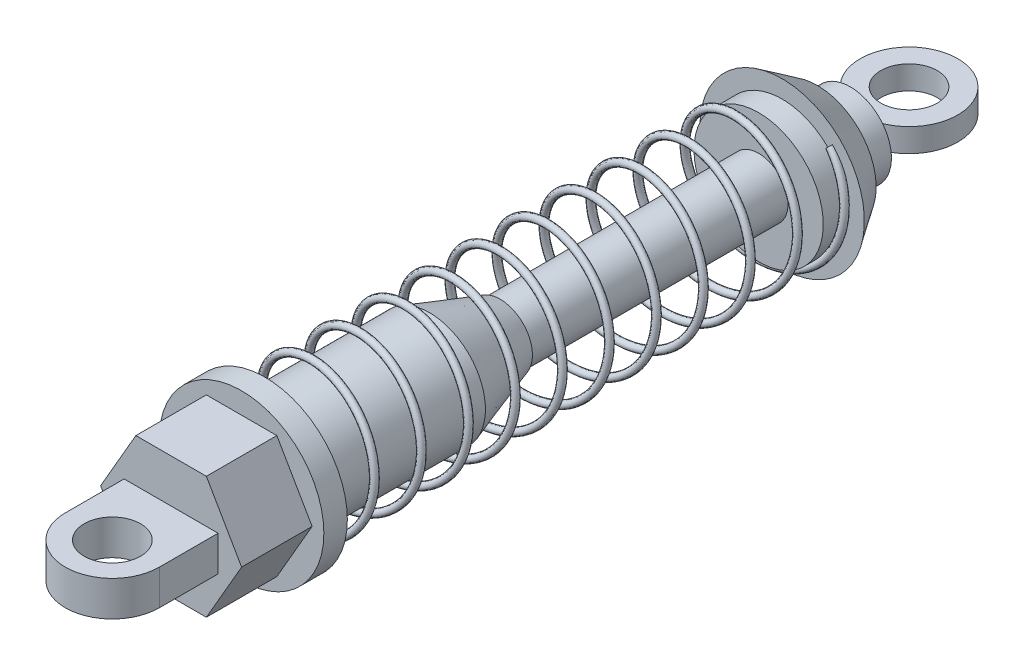
SolidWorks part; units mm, degrees
ref_plane "Alzado" through (0, 0, 0) normal (0, 0, 1) x (1, 0, 0)
ref_plane "Planta" through (0, 0, 0) normal (0, 1, 0) x (1, 0, 0)
ref_plane "Vista lateral" through (0, 0, 0) normal (1, 0, 0) x (0, 0, -1)
sketch "Croquis1" plane through (0, 0, 0) normal (0, 0, 1) x (1, 0, 0)
  circle A0 centre (0, 0) radius 7
  dimension "D1" = 14
extrude "Saliente-Extruir1" add sketch "Croquis1" along normal blind 2
sketch "Croquis2" plane through (0, 0, 2) normal (0, 0, 1) x (1, 0, 0)
  line L0 (0, 0) -> (-6, 0) construction
  line L1 (-3, 5.1962) -> (-6, 0)
  line L2 (-6, 0) -> (-3, -5.1962)
  line L3 (-3, -5.1962) -> (3, -5.1962)
  line L4 (3, -5.1962) -> (6, 0)
  line L5 (6, 0) -> (3, 5.1962)
  line L6 (3, 5.1962) -> (-3, 5.1962)
  dimension "D1" = 6
extrude "Saliente-Extruir2" add sketch "Croquis2" along normal blind 6
sketch "Croquis4" plane through (0, 0, 0) normal (0, 1, 0) x (1, 0, 0)
  line L0 (-6, -8) -> (-4, -8) construction
  line L1 (-3, -8) -> (-6, -8) construction
  line L3 (-4, -8) -> (4, -8)
  line L4 (-4, -8) -> (-4, -13)
  line L6 (4, -8) -> (4, -13)
  arc A0 (-4, -13) -> (4, -13) centre (0, -13) ccw
  dimension "D1" = 2
  dimension "D2" = 8
  dimension "D3" = 5
extrude "Saliente-Extruir3" add sketch "Croquis4" along normal mid plane 3
sketch "Croquis6" plane through (0, 1.5, 0) normal (0, 1, 0) x (1, 0, 0)
  circle A0 centre (0, -13) radius 2.4
  dimension "D1" = 4.8
extrude "Cortar-Extruir1" cut sketch "Croquis6" against normal blind 3
sketch "Croquis7" plane through (0, 0, 0) normal (0, 0, -1) x (-1, 0, 0)
  circle A0 centre (0, 0) radius 4.75
  dimension "D1" = 9.5
extrude "Saliente-Extruir4" add sketch "Croquis7" along normal blind 20
sketch "Croquis8" plane through (0, 0, -20) normal (0, 0, -1) x (-1, 0, 0)
  circle A0 centre (0, 0) radius 2.5
  dimension "D1" = 5
extrude "Cortar-Extruir2" cut sketch "Croquis8" against normal blind 20
sketch "Croquis9" plane through (0, 0, 0) normal (0, 0, -1) x (-1, 0, 0)
  circle A0 centre (0, 0) radius 5.75
  dimension "D1" = 11.5
curve "Hélice/Espiral1" pitch 4 height 44 turns 11
sketch "Croquis12" plane through (0, 0, 0) normal (1, 0, 0) x (0, 0, -1)
  circle A0 centre (0.5101, 5.7492) radius 0.3
  spline S0 degree 3 poles (0, 4.0659) (0.0828, 4.5947) (0.2502, 5.4521) (0.4999, 5.8993) (0.75, 5.4507) (1, 4.1717) (1.25, 2.2577) (1.5, 0) (1.75, -2.2577) (2, -4.1717) (2.25, -5.4506) (2.5, -5.8997) (2.75, -5.4506) (3, -4.1717) (3.3333, -1.6197) (3.6667, 1.6197) (4, 4.1717) (4.25, 5.4506) (4.5, 5.8997) (4.75, 5.4506) (5, 4.1717) (5.3333, 1.6197) (5.6667, -1.6197) (6, -4.1717) (6.25, -5.4506) (6.5, -5.8997) (6.75, -5.4506) (7, -4.1717) (7.3333, -1.6197) (7.6667, 1.6197) (8, 4.1717) (8.25, 5.4506) (8.5, 5.8997) (8.75, 5.4506) (9, 4.1717) (9.3333, 1.6197) (9.6667, -1.6197) (10, -4.1717) (10.25, -5.4506) (10.5, -5.8997) (10.75, -5.4506) (11, -4.1717) (11.3333, -1.6197) (11.6667, 1.6197) (12, 4.1717) (12.25, 5.4506) (12.5, 5.8997) (12.75, 5.4506) (13, 4.1717) (13.3333, 1.6197) (13.6667, -1.6197) (14, -4.1717) (14.25, -5.4506) (14.5, -5.8997) (14.75, -5.4506) (15, -4.1717) (15.3333, -1.6197) (15.6667, 1.6197) (16, 4.1717) (16.25, 5.4506) (16.5, 5.8997) (16.75, 5.4506) (17, 4.1717) (17.3333, 1.6197) (17.6667, -1.6197) (18, -4.1717) (18.25, -5.4506) (18.5, -5.8997) (18.75, -5.4506) (19, -4.1717) (19.3333, -1.6197) (19.6667, 1.6197) (20, 4.1717) (20.25, 5.4506) (20.5, 5.8997) (20.75, 5.4506) (21, 4.1717) (21.3333, 1.6197) (21.6667, -1.6197) (22, -4.1717) (22.25, -5.4506) (22.5, -5.8997) (22.75, -5.4506) (23, -4.1717) (23.3333, -1.6197) (23.6667, 1.6197) (24, 4.1717) (24.25, 5.4506) (24.5, 5.8997) (24.75, 5.4506) (25, 4.1717) (25.3333, 1.6197) (25.6667, -1.6197) (26, -4.1717) (26.25, -5.4506) (26.5, -5.8997) (26.75, -5.4506) (27, -4.1717) (27.3333, -1.6197) (27.6667, 1.6197) (28, 4.1717) (28.25, 5.4506) (28.5, 5.8997) (28.75, 5.4506) (29, 4.1717) (29.3333, 1.6197) (29.6667, -1.6197) (30, -4.1717) (30.25, -5.4506) (30.5, -5.8997) (30.75, -5.4506) (31, -4.1717) (31.3333, -1.6197) (31.6667, 1.6197) (32, 4.1717) (32.25, 5.4506) (32.5, 5.8997) (32.75, 5.4506) (33, 4.1717) (33.3333, 1.6197) (33.6667, -1.6197) (34, -4.1717) (34.25, -5.4506) (34.5, -5.8997) (34.75, -5.4506) (35, -4.1717) (35.3333, -1.6197) (35.6667, 1.6197) (36, 4.1717) (36.25, 5.4506) (36.5, 5.8997) (36.75, 5.4506) (37, 4.1717) (37.3333, 1.6197) (37.6667, -1.6197) (38, -4.1717) (38.25, -5.4506) (38.5, -5.8997) (38.75, -5.4506) (39, -4.1717) (39.3333, -1.6197) (39.6667, 1.6197) (40, 4.1717) (40.25, 5.4506) (40.5, 5.8997) (40.75, 5.4506) (41, 4.1717) (41.3333, 1.6197) (41.6667, -1.6197) (42, -4.1717) (42.25, -5.4506) (42.5, -5.8997) (42.75, -5.4506) (43, -4.1717) (43.25, -2.2578) (43.5001, 0.0004) (43.7498, 2.2562) (43.9172, 3.537) (44, 4.0659) knots 0 0 0 0 0.005682 0.011364 0.017045 0.022727 0.028409 0.034091 0.039773 0.045455 0.051136 0.056818 0.0625 0.068182 0.073864 0.085227 0.090909 0.096591 0.102273 0.107955 0.113636 0.119318 0.130682 0.136364 0.142045 0.147727 0.153409 0.159091 0.164773 0.176136 0.181818 0.1875 0.193182 0.198864 0.204545 0.210227 0.221591 0.227273 0.232955 0.238636 0.244318 0.25 0.255682 0.267045 0.272727 0.278409 0.284091 0.289773 0.295455 0.301136 0.3125 0.318182 0.323864 0.329545 0.335227 0.340909 0.346591 0.357955 0.363636 0.369318 0.375 0.380682 0.386364 0.392045 0.403409 0.409091 0.414773 0.420455 0.426136 0.431818 0.4375 0.448864 0.454545 0.460227 0.465909 0.471591 0.477273 0.482955 0.494318 0.5 0.505682 0.511364 0.517045 0.522727 0.528409 0.539773 0.545455 0.551136 0.556818 0.5625 0.568182 0.573864 0.585227 0.590909 0.596591 0.602273 0.607955 0.613636 0.619318 0.630682 0.636364 0.642045 0.647727 0.653409 0.659091 0.664773 0.676136 0.681818 0.6875 0.693182 0.698864 0.704545 0.710227 0.721591 0.727273 0.732955 0.738636 0.744318 0.75 0.755682 0.767045 0.772727 0.778409 0.784091 0.789773 0.795455 0.801136 0.8125 0.818182 0.823864 0.829545 0.835227 0.840909 0.846591 0.857955 0.863636 0.869318 0.875 0.880682 0.886364 0.892045 0.903409 0.909091 0.914773 0.920455 0.926136 0.931818 0.9375 0.948864 0.954545 0.960227 0.965909 0.971591 0.977273 0.982955 0.988636 0.994318 1 1 1 1 construction
  dimension "D1" = 0.6
sweep "Barrer1" add profiles "Croquis12" path "Hélice/Espiral1"
ref_plane "Plano1" through (0, 0, -44) normal (0, 0, -1) x (-1, 0, 0)
sketch "Croquis13" plane through (0, 0, -44) normal (0, 0, -1) x (-1, 0, 0)
  circle A0 centre (0, 0) radius 7
extrude "Saliente-Extruir5" add sketch "Croquis13" along normal blind 3
sketch "Croquis14" plane through (0, 0, 0) normal (1, 0, 0) x (0, 0, -1)
  line L0 (20, -4.75) -> (20, -2.75)
  line L1 (20, -4.75) -> (20, 4.75) construction
  line L2 (20, -2.75) -> (14, -4.75)
  line L3 (0, -4.75) -> (20, -4.75) construction
  line L4 (14, -4.75) -> (20, -4.75)
  line L5 (20, 0) -> (0, 0) construction
  dimension "D1" = 6
  dimension "D2" = 2
revolve "Cortar-Revolución1" cut sketch "Croquis14" angle 360 about L5
sketch "Croquis15" plane through (0, 0, -44) normal (0, 0, 1) x (1, 0, 0)
  circle A0 centre (0, 0) radius 5.5
  dimension "D1" = 11
extrude "Saliente-Extruir6" add sketch "Croquis15" along normal blind 2
sketch "Croquis16" plane through (0, 0, -42) normal (0, 0, 1) x (1, 0, 0)
  circle A0 centre (0, 0) radius 2.5
  dimension "D1" = 5
extrude "Saliente-Extruir7" add sketch "Croquis16" along normal blind 24
sketch "Croquis17" plane through (0, 0, 0) normal (1, 0, 0) x (0, 0, -1)
  line L0 (47, -7) -> (44, -7)
  line L1 (44, -7.7) -> (44, 7.7) construction
  line L2 (44, -7) -> (47, -7) construction
  line L3 (44, -7) -> (47, -5)
  line L4 (47, -7) -> (47, 7) construction
  line L5 (47, -5) -> (47, -7)
  line L6 (47, 0) -> (30.7221, 0) construction
  dimension "D1" = 2
revolve "Cortar-Revolución2" cut sketch "Croquis17" angle 360 about L6
sketch "Croquis18" plane through (0, 0, -47) normal (0, 0, -1) x (-1, 0, 0)
  circle A0 centre (0, 0) radius 3.5
  dimension "D1" = 7
extrude "Saliente-Extruir8" add sketch "Croquis18" along normal blind 2.8
sketch "Croquis19" plane through (0, 0, 0) normal (0, 1, 0) x (1, 0, 0)
  line L0 (-3.5, 49.8) -> (-1.5, 49.8) construction
  line L1 (3.5, 49.8) -> (-3.5, 49.8) construction
  line L2 (0, 49.8) -> (0, 49.85) construction
  line L3 (-1.5, 49.8) -> (1.5, 49.8)
  line L4 (-1.5, 49.8) -> (-1.5, 50.9306)
  line L6 (1.5, 49.8) -> (1.5, 50.9306)
  arc A0 (1.5, 50.9306) -> (-1.5, 50.9306) centre (0, 54.8) ccw
  circle A1 centre (0, 54.8) radius 2.4
  dimension "D4" = 4.8
  dimension "D5" = 8.3
  dimension "D1" = 2
  dimension "D2" = 3
  dimension "D3" = 5
  dimension "D6" = 1.1306
extrude "Saliente-Extruir9" add sketch "Croquis19" along normal mid plane 2
